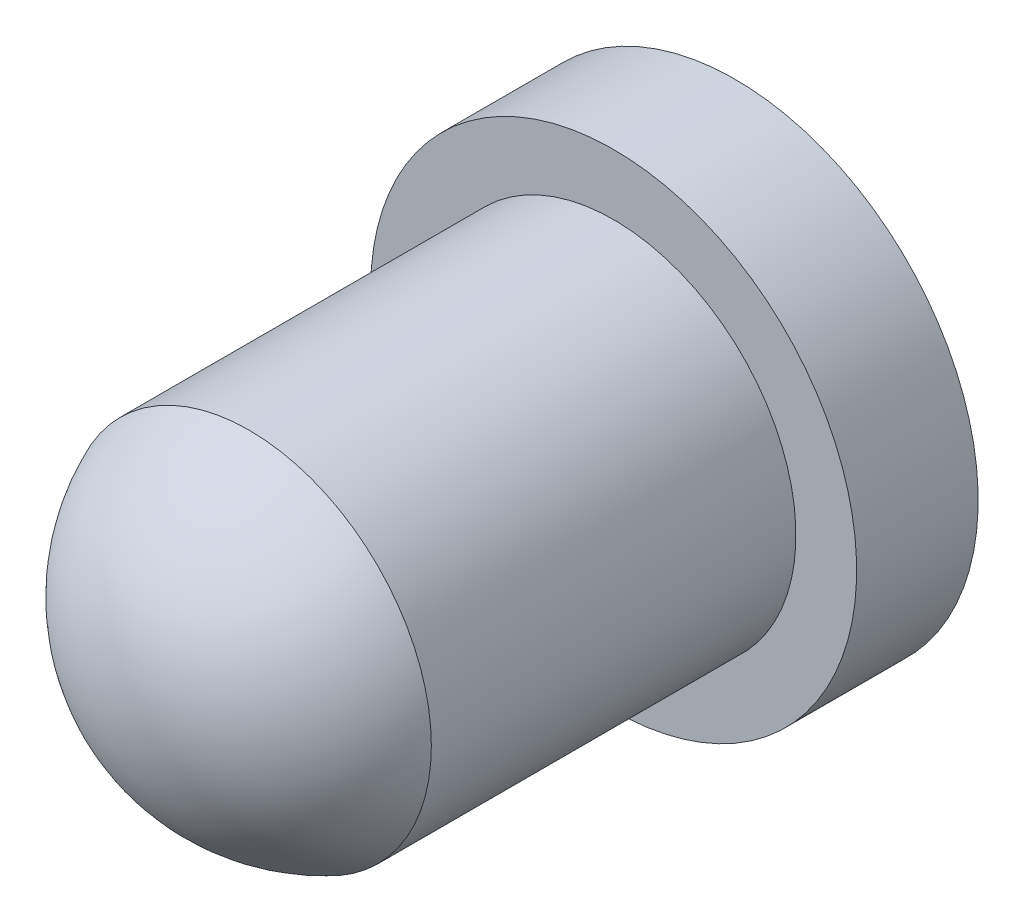
SolidWorks part; units mm, degrees
ref_plane "前视基准面" through (0, 0, 0) normal (0, 0, 1) x (1, 0, 0)
ref_plane "上视基准面" through (0, 0, 0) normal (0, 1, 0) x (1, 0, 0)
ref_plane "右视基准面" through (0, 0, 0) normal (1, 0, 0) x (0, 0, -1)
sketch "草图1" plane through (0, 0, 0) normal (0, 0, 1) x (1, 0, 0)
  circle A0 centre (0, 0) radius 1.5
  dimension "D1" = 3
extrude "拉伸1" add sketch "草图1" along normal blind 3
sketch "草图2" plane through (0, 0, 0) normal (0, 0, -1) x (-1, 0, 0)
  circle A0 centre (0, 0) radius 2
  dimension "D1" = 4
extrude "拉伸2" add sketch "草图2" along normal blind 1
dome "圆顶1" faces to dome 1 distance 1 reverse direction no elliptical dome no face at (1.5, 0, 3) parameters "D1"=1
